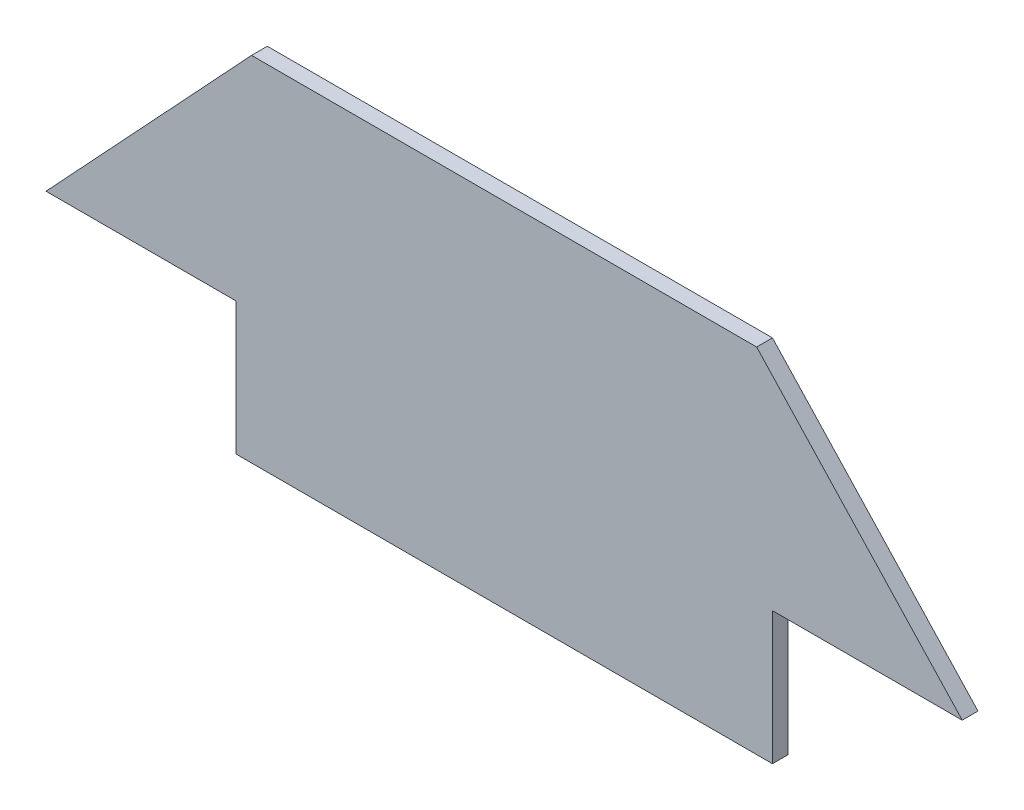
SolidWorks part; units mm, degrees
ref_plane "前视基准面" through (0, 0, 0) normal (0, 0, 1) x (1, 0, 0)
ref_plane "上视基准面" through (0, 0, 0) normal (0, 1, 0) x (1, 0, 0)
ref_plane "右视基准面" through (0, 0, 0) normal (1, 0, 0) x (0, 0, -1)
sketch "草图1" plane through (0, 0, 0) normal (0, 0, 1) x (1, 0, 0)
  line L0 (-80, 0) -> (80, 0)
  line L1 (80, 0) -> (145.1093, -69.8212)
  line L2 (145.1093, -69.8212) -> (85, -69.8212)
  line L3 (85, -69.8212) -> (85, -111.8212)
  line L4 (85, -111.8212) -> (-85, -111.8212)
  line L5 (0, -111.8212) -> (0, 0)
  line L6 (-85, -69.8212) -> (-85, -111.8212)
  line L7 (-145.1093, -69.8212) -> (-85, -69.8212)
  line L8 (-80, 0) -> (-145.1093, -69.8212)
  dimension "D1" = 80
  dimension "D2" = 133
  dimension "D3" = 85
  dimension "D4" = 70
  dimension "D5" = 42
extrude "凸台-拉伸1" add sketch "草图1" along normal blind 5 contours L0 L8 L7 L6 L4 L5 | L5 L4 L3 L2 L1 L0 region at (-53.0528, -54.6899, 0) region at (53.0528, -54.6899, 0)
